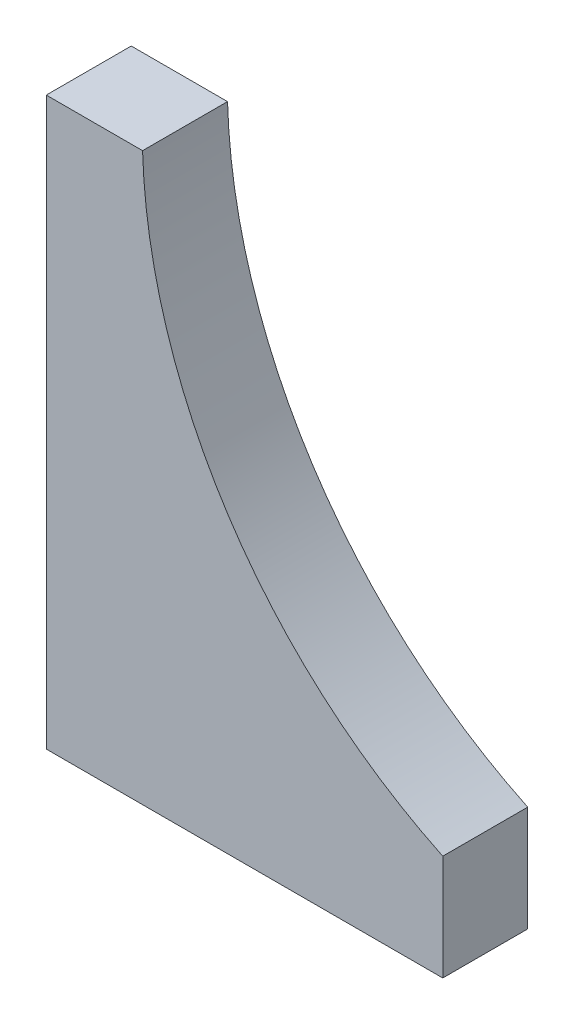
SolidWorks part; units mm, degrees
ref_plane "Plan de face" through (0, 0, 0) normal (0, 0, 1) x (1, 0, 0)
ref_plane "Plan de dessus" through (0, 0, 0) normal (0, 1, 0) x (1, 0, 0)
ref_plane "Plan de droite" through (0, 0, 0) normal (1, 0, 0) x (0, 0, -1)
sketch "Esquisse1" plane through (0, 0, 0) normal (0, 0, 1) x (1, 0, 0)
  line L0 (0, 100) -> (17, 100)
  line L1 (0, 0) -> (70, 0)
  line L2 (0, 0) -> (0, 100)
  line L4 (70, 0) -> (70, 18.6251)
  arc A1 (17, 100) -> (70, 18.6251) centre (110.2624, 102.7954) ccw
  dimension "D3" = 17
  dimension "D6" = 93.3042
  dimension "D1" = 100
  dimension "D2" = 70
  dimension "D4" = 110.2624
  dimension "D5" = 102.7954
extrude "Boss.-Extru.1" add sketch "Esquisse1" along normal blind 15
sketch "Esquisse5" plane through (0, 0, 0) normal (-1, 0, 0) x (0, 0, 1)
  line L1 (0, 100) -> (0, 0) construction
  circle A0 centre (7.5, 85) radius 2.5
  dimension "D1" = 15
  dimension "D3" = 5
  dimension "D2" = 7.5
sketch "Esquisse7" plane through (0, 0, 0) normal (-1, 0, 0) x (0, 0, 1)
  line L0 (15, 0) -> (0, 0) construction
  circle A0 centre (7.5, 25) radius 2.5
  dimension "D1" = 5
  dimension "D2" = 25
  dimension "D3" = 7.5
extrude "Enlèv. mat.-Extru.4" cut sketch "Esquisse7" against normal blind 16
extrude "Enlèv. mat.-Extru.5" cut sketch "Esquisse5" against normal blind 16
sketch "Esquisse8" plane through (0, 0, 0) normal (0, -1, 0) x (1, 0, 0)
  circle A0 centre (20, 7.5) radius 2.5
  dimension "D1" = 5
  dimension "D2" = 20
  dimension "D3" = 7.5
extrude "Enlèv. mat.-Extru.6" cut sketch "Esquisse8" against normal blind 16
sketch "Esquisse9" plane through (0, 0, 0) normal (0, -1, 0) x (1, 0, 0)
  circle A0 centre (55, 7.5) radius 2.5
  dimension "D1" = 5
  dimension "D2" = 7.5
  dimension "D3" = 15
extrude "Enlèv. mat.-Extru.7" cut sketch "Esquisse9" against normal blind 16
